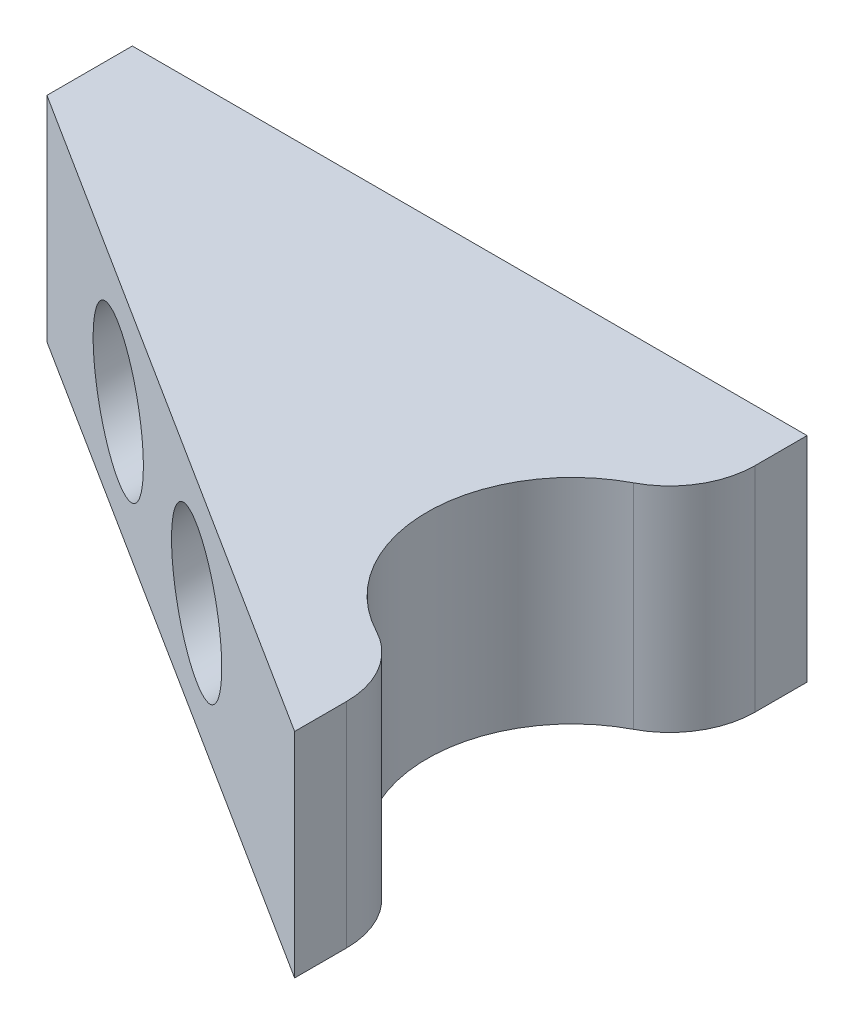
SolidWorks part; units mm, degrees
note: The reader was unsure of these and kept them because the rebuilt part matched: shared geometry of "Sketch1<3>".
material "1023 Carbon Steel Sheet (SS)"
ref_plane "Front Plane" through (0, 0, 0) normal (0, 0, 1) x (1, 0, 0)
ref_plane "Top Plane" through (0, 0, 0) normal (0, 1, 0) x (1, 0, 0)
ref_plane "Right Plane" through (0, 0, 0) normal (1, 0, 0) x (0, 0, -1)
sketch "Sketch1" plane through (0, 0, 0) normal (0, 0, 1) x (1, 0, 0)
  line L1 (-25.0825, -7.9375) -> (25.0825, -7.9375)
  line L2 (-25.0825, -7.9375) -> (-25.0825, 7.9375)
  line L3 (-25.0825, 7.9375) -> (25.0825, 7.9375)
  line L4 (25.0825, -7.9375) -> (25.0825, 7.9375)
  line L5 (-25.0825, -7.9375) -> (25.0825, 7.9375) construction
  line L6 (-25.0825, 7.9375) -> (25.0825, -7.9375) construction
  circle A0 centre (5.2387, 0) radius 3.302
  circle A1 centre (-10.6363, 0) radius 3.302
  point P0 (0, 0)
  dimension "D3" = 6.604
  dimension "D4" = 15.875
  dimension "D1" = 50.165
  dimension "D2" = 15.875
  dimension "D5" = 19.8438
extrude "Boss-Extrude1" add sketch "Sketch1" along normal blind 6.35 contours L3 L4 L1 L2 | A1 | A0
sketch "Sketch4" plane through (0, -7.9375, 0) normal (0, -1, 0) x (1, 0, 0)
  line L0 (25.0825, 6.35) -> (25.0825, 44.45)
  line L1 (25.0825, 44.45) -> (-3.4925, 44.45)
  line L2 (6.0325, 44.45) -> (25.0825, 38.1)
  line L3 (-25.0825, 6.35) -> (-0.4735, 38.3158)
  line L4 (25.0825, 38.1) -> (-0.6397, 38.1)
  line L5 (-25.0825, 6.35) -> (25.0825, 38.1)
  circle A0 centre (25.0825, 19.05) radius 10.668
  circle A1 centre (-3.4925, 40.64) radius 3.81
  arc A2 (25.0825, 29.718) -> (25.0825, 8.382) centre (26.67, 19.05) ccw
  line M8 (25.0825, 6.35) -> (-25.0825, 6.35)
  dimension "D3" = 21.336
  dimension "D4" = 7.62
  dimension "D5" = 31.75
  dimension "D8" = 1.5875
  dimension "D1" = 28.575
  dimension "D2" = 38.1
  dimension "D6" = 12.7
  dimension "D7" = 19.05
  dimension "D9" = 21.336
extrude "Boss-Extrude2" add sketch "Sketch4" against normal through all contours A1 L3 L0 A0 L1 M8 | A2 A0
fillet "Fillet1" radius 6.35 1 edges at (25.0825, 0, 29.718)
sketch "Sketch7" plane through (0, 0, 0) normal (0, 1, 0) x (1, 0, 0)
  line L0 (-25.0825, -6.35) -> (2.4515, -35.483)
  line L1 (25.0825, -38.1) -> (2.4703, -43.1877)
  line L3 (-25.0825, 0) -> (25.0825, 0) construction
  line L4 (25.0825, -3.8638) -> (25.0825, 0) construction
  line L5 (-25.0825, -6.35) -> (25.0825, -38.1)
  circle A0 centre (-0.3175, -38.1) radius 3.81
  circle A1 centre (-0.3175, -30.7975) radius 12.7
  circle A2 centre (-0.3175, -42.7037) radius 0.7937
  dimension "D1" = 7.62
  dimension "D2" = 1.5875
  dimension "D3" = 38.1
  dimension "D5" = 25.4
  dimension "D4" = 25.4
extrude "Boss-Extrude3" [suppressed] add sketch "Sketch7" along normal mid plane 6.35
extrude "Cut-Extrude1" cut sketch "Sketch1<3>" along normal through all contours A0 | A1
sketch "Sketch1<3>" plane through (0, 0, 0) normal (0, 0, 1) x (1, 0, 0) same geometry as "Sketch1"
ref_plane "Plane2" through (0, 0, 6.35) normal (0, 0, -1) x (-1, 0, 0)
sketch "Sketch10" plane through (0, 0, 6.35) normal (0, 0, -1) x (-1, 0, 0)
  circle A0 centre (10.6363, 0) radius 5.08
  circle A1 centre (-5.2387, 0) radius 5.08
  dimension "D1" = 10.16
extrude "Cut-Extrude4" cut sketch "Sketch10" against normal through all
